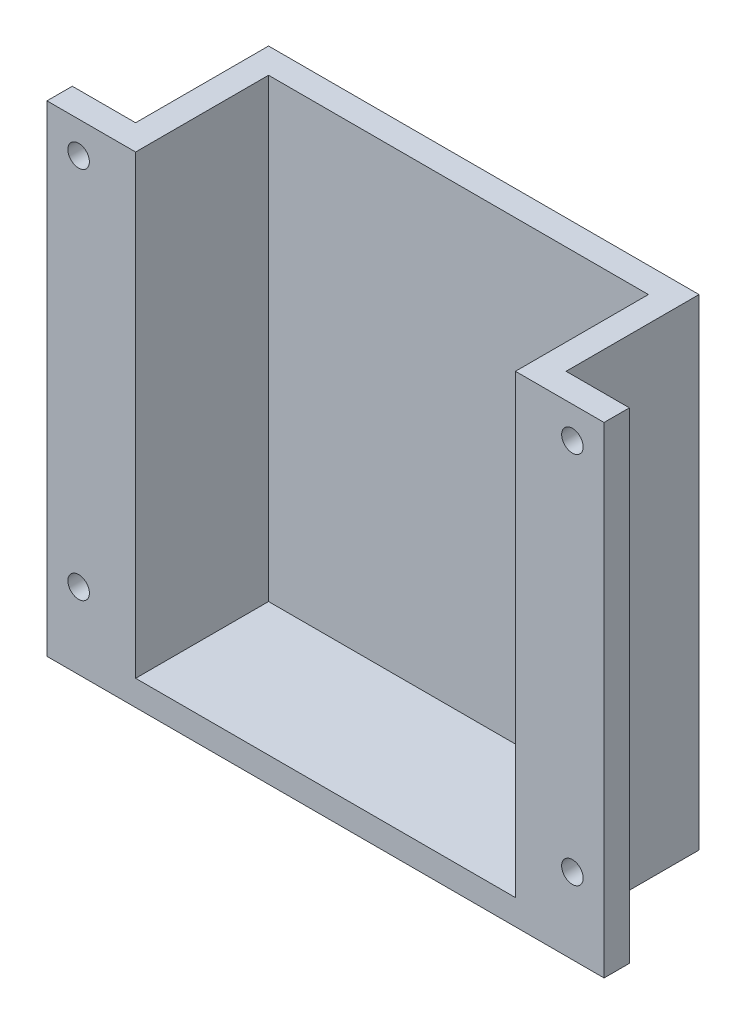
SolidWorks part; units mm, degrees
ref_plane "Front Plane" through (0, 0, 0) normal (0, 0, 1) x (1, 0, 0)
ref_plane "Top Plane" through (0, 0, 0) normal (0, 1, 0) x (1, 0, 0)
ref_plane "Right Plane" through (0, 0, 0) normal (1, 0, 0) x (0, 0, -1)
sketch "Sketch1" plane through (0, 0, 0) normal (0, 1, 0) x (1, 0, 0)
  line L0 (-48.1667, 0) -> (-38.1667, 0)
  line L1 (-38.1667, 0) -> (-38.1667, 21)
  line L2 (-38.1667, 21) -> (29.8333, 21)
  line L3 (29.8333, 21) -> (29.8333, 0)
  line L4 (29.8333, 0) -> (39.8333, 0)
  line L5 (-48.1667, 0) -> (-48.1667, -4)
  line L6 (-48.1667, -4) -> (-34.1667, -4)
  line L7 (-34.1667, -4) -> (-34.1667, 17)
  line L8 (-34.1667, 17) -> (25.8333, 17)
  line L9 (25.8333, 17) -> (25.8333, -4)
  line L10 (25.8333, -4) -> (39.8333, -4)
  line L11 (39.8333, 0) -> (39.8333, -4)
  dimension "D1" = 4
  dimension "D2" = 4
  dimension "D3" = 4
  dimension "D4" = 21
  dimension "D5" = 10
  dimension "D6" = 4
  dimension "D7" = 14
  dimension "D8" = 21
  dimension "D9" = 60
  dimension "D10" = 14
  dimension "D11" = 4
extrude "Boss-Extrude1" add sketch "Sketch1" along normal blind 76 contours L11 L10 L9 L8 L7 L6 L5 L0 L1 L2 L3 L4
sketch "Sketch2" plane through (0, 0, -17) normal (0, 0, 1) x (1, 0, 0)
  line L0 (-34.1667, 4) -> (25.8333, 4)
  line L1 (-34.1667, 76) -> (-34.1667, 0) construction
  line L2 (25.8333, 76) -> (25.8333, 0) construction
  line L3 (-34.1667, 0) -> (25.8333, 0) construction
  dimension "D1" = 4
extrude "Extrude-Thin1" add sketch "Sketch2" along normal blind 21 thin thin type one direction wall 4
sketch "Sketch4" plane through (0, 0, 0) normal (0, 0, -1) x (-1, 0, 0)
  line L0 (-29.8333, 76) -> (-39.8333, 76) construction
  line L1 (-39.8333, 76) -> (-39.8333, 0) construction
  line L2 (-29.8333, 0) -> (-39.8333, 0) construction
  line L3 (48.1667, 76) -> (38.1667, 76) construction
  line L4 (48.1667, 76) -> (48.1667, 0) construction
  line L5 (48.1667, 0) -> (38.1667, 0) construction
  circle A0 centre (-34.8333, 71) radius 1.7
  circle A1 centre (-34.8333, 12) radius 1.7
  circle A2 centre (43.1667, 71) radius 1.7
  circle A3 centre (43.1667, 12) radius 1.7
  dimension "D1" = 5
  dimension "D3" = 3.4
  dimension "D4" = 5
  dimension "D6" = 3.4
  dimension "D7" = 5
  dimension "D9" = 5
  dimension "D2" = 5
  dimension "D5" = 12
  dimension "D8" = 5
  dimension "D10" = 12
extrude "Cut-Extrude1" cut sketch "Sketch4" against normal blind 21
